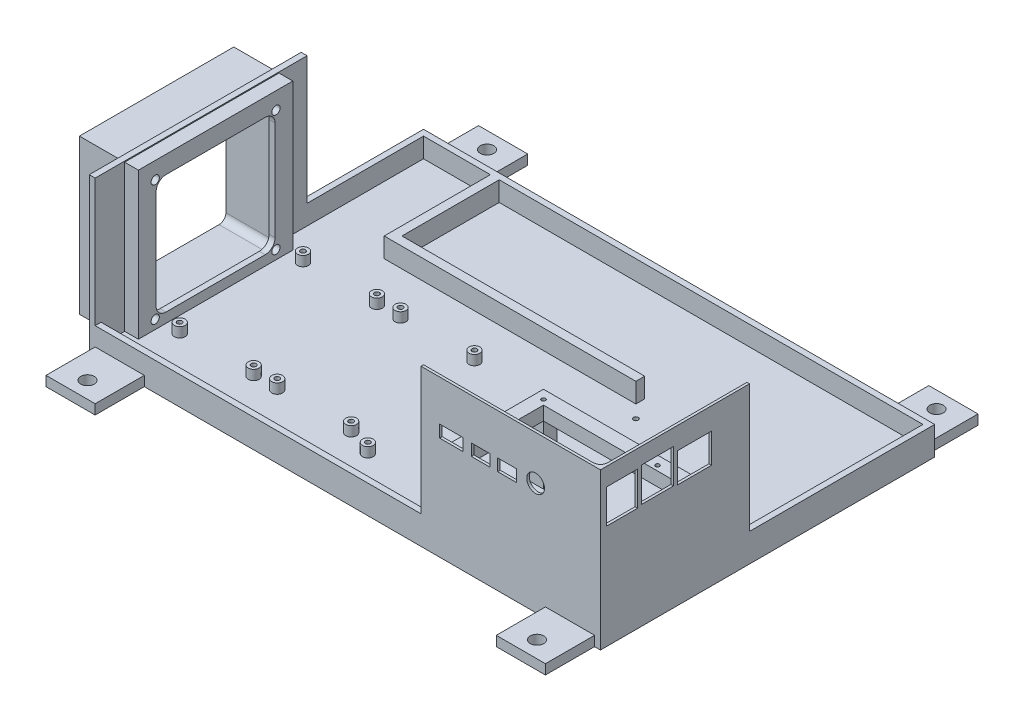
SolidWorks part; units mm, degrees
ref_plane "Front Plane" through (0, 0, 0) normal (0, 0, 1) x (1, 0, 0)
ref_plane "Top Plane" through (0, 0, 0) normal (0, 1, 0) x (1, 0, 0)
ref_plane "Right Plane" through (0, 0, 0) normal (1, 0, 0) x (0, 0, -1)
sketch "Sketch1" plane through (0, 0, 0) normal (0, 1, 0) x (1, 0, 0)
  line L1 (-130, -85) -> (130, -85)
  line L2 (-130, -85) -> (-130, 85)
  line L3 (-130, 85) -> (130, 85)
  line L4 (130, -85) -> (130, 85)
  line L5 (-130, -85) -> (130, 85) construction
  line L6 (-130, 85) -> (130, -85) construction
  point P0 (0, 0)
  dimension "D1" = 170
  dimension "D2" = 260
extrude "Floor" add sketch "Sketch1" along normal blind 4.3805
sketch "Sketch2" plane through (0, 4.3805, 0) normal (0, 1, 0) x (1, 0, 0)
  line L0 (127, -82) -> (127, 82)
  line L1 (127, 82) -> (-127, 82)
  line L2 (-127, 82) -> (-127, -82)
  line L3 (-127, -82) -> (127, -82)
  line L4 (130, -85) -> (130, 85)
  line L5 (130, 85) -> (-130, 85)
  line L6 (-130, 85) -> (-130, -85)
  line L7 (-130, -85) -> (130, -85)
  line L8 (130, -85) -> (130, 85)
  line L9 (130, 85) -> (-130, 85)
  line L10 (-130, 85) -> (-130, -85)
  line L11 (-130, -85) -> (130, -85)
  dimension "D1" = 0
  dimension "D2" = 3
extrude "Wall" add sketch "Sketch2" along normal blind 10
sketch "Sketch4" plane through (0, 4.3805, 0) normal (0, 1, 0) x (1, 0, 0)
  line L0 (120, -33) -> (49, -33)
  line L1 (127, -82) -> (42, -82)
  line L2 (127, -82) -> (127, -26)
  line L3 (127, -26) -> (42, -26)
  line L4 (42, -82) -> (42, -26)
  line L5 (49, -75) -> (49, -33)
  line L6 (120, -75) -> (49, -75)
  line L7 (120, -75) -> (120, -33)
  dimension "D1" = 85
  dimension "D2" = 56
  dimension "D3" = 7
extrude "Rpi stand" add sketch "Sketch4" along normal blind 7 from offset 30
sketch "Sketch7" plane through (0, 14.3805, 0) normal (0, 1, 0) x (1, 0, 0)
  line L0 (-127, 82) -> (-127, -82) construction
  line L1 (-130, -85) -> (-127, -85)
  line L2 (-130, -85) -> (-130, 22.7839)
  line L3 (-130, 22.7839) -> (-127, 22.7839)
  line L4 (-127, -85) -> (-127, 22.7839)
  line L5 (-127, -82) -> (127, -82) construction
  line L6 (130, -85) -> (38.7223, -85)
  line L7 (130, -85) -> (130, -52.9248)
  line L8 (127, -82) -> (38.7223, -82)
  line L9 (38.7223, -85) -> (38.7223, -82)
  line L10 (127, -82) -> (127, 82) construction
  line L12 (130, -52.9248) -> (130, -9.2525)
  line L13 (130, -9.2525) -> (127, -9.2525)
  line L14 (127, -82) -> (127, -9.2525)
  line L15 (-127, -82) -> (127, -82) construction
  line L16 (130, -85) -> (130, 85) construction
extrude "Temp support" add sketch "Sketch7" along normal blind 65
sketch "Sketch3" plane through (0, 0, 0) normal (0, 1, 0) x (1, 0, 0)
  line L0 (-114.3, 101.6) -> (114.3, 101.6) construction
  line L1 (-127, 85) -> (-102, 85)
  line L2 (-127, 85) -> (-127, 110)
  line L3 (-127, 110) -> (-102, 110)
  line L4 (-102, 85) -> (-102, 110)
  line L5 (127, 85) -> (102, 85)
  line L6 (127, 85) -> (127, 110)
  line L7 (127, 110) -> (102, 110)
  line L8 (102, 85) -> (102, 110)
  line L9 (-127, -85) -> (-102, -85)
  line L10 (-127, -85) -> (-127, -110)
  line L11 (-127, -110) -> (-102, -110)
  line L12 (-102, -85) -> (-102, -110)
  line L13 (127, -85) -> (102, -85)
  line L14 (127, -85) -> (127, -110)
  line L15 (127, -110) -> (102, -110)
  line L16 (102, -85) -> (102, -110)
  line L17 (114.3, 101.6) -> (114.3, -101.6) construction
  line L18 (114.3, -101.6) -> (-114.3, -101.6) construction
  line L19 (-114.3, -101.6) -> (-114.3, 101.6) construction
  line L20 (-130, 37.8738) -> (130, 37.8738) construction
  line L21 (130, 85) -> (-130, 85) construction
  line L22 (130, -9.2525) -> (130, 85) construction
  line L23 (0, 101.6) -> (0, -101.6) construction
  line L24 (-130, 22.7839) -> (-130, -85) construction
  line L29 (38.7223, -85) -> (130, -85) construction
  line L30 (-127, -85) -> (38.7223, -85) construction
  circle A0 centre (-114.3, 101.6) radius 3.429
  circle A1 centre (114.3, 101.6) radius 3.429
  circle A2 centre (114.3, -101.6) radius 3.429
  circle A3 centre (-114.3, -101.6) radius 3.429
  point P28 (-114.5, -85)
  point P29 (-102, -97.5)
  point P30 (114.5, -85)
  point P31 (-102, 97.5)
  dimension "D5" = 6.858
  dimension "D1" = 25
  dimension "D2" = 25
  dimension "D3" = 25
  dimension "D6" = 203.2
  dimension "D7" = 228.6
  dimension "D8" = 3
  dimension "D9" = 3
  dimension "D4" = 25
extrude "Brackets" add sketch "Sketch3" along normal blind 5
sketch "Sketch5" plane through (-130, 0, 0) normal (-1, 0, 0) x (0, 0, 1)
  line L0 (-8.5, 78.8805) -> (70, 78.8805)
  line L1 (-1, 4.3805) -> (62.5, 4.3805)
  line L2 (-4.5, 7.8805) -> (-4.5, 71.3805)
  line L3 (-1, 74.8805) -> (62.5, 74.8805)
  line L4 (66, 7.8805) -> (66, 71.3805)
  line L5 (70, 0.3805) -> (70, 78.8805)
  line L6 (-8.5, 0.3805) -> (70, 0.3805)
  line L7 (-8.5, 0.3805) -> (-8.5, 78.8805)
  line L8 (-4.5, 4.3805) -> (66, 4.3805) construction
  line L9 (110, 5) -> (110, 0) construction
  line L10 (-4.5, 4.3805) -> (-4.5, 74.8805) construction
  line L11 (-82, 4.3805) -> (82, 4.3805) construction
  line L12 (66, 4.3805) -> (66, 74.8805) construction
  line L13 (-4.5, 74.8805) -> (66, 74.8805) construction
  arc A0 (-1, 4.3805) -> (-4.5, 7.8805) centre (-1, 7.8805) cw
  arc A1 (62.5, 4.3805) -> (66, 7.8805) centre (62.5, 7.8805) ccw
  arc A2 (62.5, 74.8805) -> (66, 71.3805) centre (62.5, 71.3805) cw
  arc A3 (-4.5, 71.3805) -> (-1, 74.8805) centre (-1, 71.3805) cw
  dimension "D4" = 3.5
  dimension "D1" = 70.5
  dimension "D2" = 70.5
  dimension "D5" = 40
  dimension "D3" = 4
extrude "Fan Holder" add sketch "Sketch5" along normal blind 20 and the other way blind 10
sketch "Sketch8" plane through (-130, 0, 0) normal (-1, 0, 0) x (0, 0, 1)
  line L4 (-4.5, 71.3805) -> (-4.5, 7.8805)
  line L5 (-1, 4.3805) -> (62.5, 4.3805)
  line L6 (66, 7.8805) -> (66, 71.3805)
  line L7 (62.5, 74.8805) -> (-1, 74.8805)
  line L8 (-4.5, 71.3805) -> (-4.5, 7.8805)
  line L9 (-1, 4.3805) -> (62.5, 4.3805)
  line L10 (66, 7.8805) -> (66, 71.3805)
  line L20 (62.5, 74.8805) -> (-1, 74.8805)
  arc A2 (-4.5, 7.8805) -> (-1, 4.3805) centre (-1, 7.8805) ccw
  arc A3 (-4.5, 7.8805) -> (-1, 4.3805) centre (-1, 7.8805) ccw
  arc A4 (62.5, 4.3805) -> (66, 7.8805) centre (62.5, 7.8805) ccw
  arc A5 (62.5, 4.3805) -> (66, 7.8805) centre (62.5, 7.8805) ccw
  arc A8 (66, 71.3805) -> (62.5, 74.8805) centre (62.5, 71.3805) ccw
  arc A12 (66, 71.3805) -> (62.5, 74.8805) centre (62.5, 71.3805) ccw
  arc A14 (-1, 74.8805) -> (-4.5, 71.3805) centre (-1, 71.3805) ccw
  arc A15 (-1, 74.8805) -> (-4.5, 71.3805) centre (-1, 71.3805) ccw
  dimension "D1" = 0
extrude "Fan hole" cut sketch "Sketch8" against normal up to next (3 mm away)
sketch "Sketch11" plane through (-120, 0, 0) normal (-1, 0, 0) x (0, 0, 1)
  line L0 (-8.5, 39.6305) -> (70, 39.6305) construction
  line L1 (30.75, 78.8805) -> (30.75, 0.3805) construction
  line L3 (0.05, 8.9305) -> (61.45, 8.9305) construction
  line L4 (-8.5, 78.8805) -> (-8.5, 0.3805)
  line L5 (-8.5, 0.3805) -> (70, 0.3805)
  line L6 (70, 0.3805) -> (70, 78.8805)
  line L7 (70, 78.8805) -> (-8.5, 78.8805)
  line L8 (-8.5, 78.8805) -> (-8.5, 0.3805)
  line L9 (-8.5, 0.3805) -> (70, 0.3805)
  line L10 (70, 0.3805) -> (70, 78.8805)
  line L11 (70, 78.8805) -> (-8.5, 78.8805)
  line L12 (0.05, 8.9305) -> (0.05, 70.3305) construction
  line L13 (0.05, 70.3305) -> (61.45, 70.3305) construction
  line L14 (61.45, 8.9305) -> (61.45, 70.3305) construction
  line L15 (0.05, 8.9305) -> (61.45, 70.3305) construction
  line L16 (0.5, 69.8805) -> (0.5, 9.3805)
  line L17 (0.5, 9.3805) -> (61, 9.3805)
  line L18 (61, 9.3805) -> (61, 69.8805)
  line L19 (61, 69.8805) -> (0.5, 69.8805)
  line L20 (0.5, 64.8805) -> (0.5, 14.3805)
  line L21 (5.5, 9.3805) -> (56, 9.3805)
  line L22 (61, 14.3805) -> (61, 64.8805)
  line L23 (56, 69.8805) -> (5.5, 69.8805)
  line L24 (0.05, 70.3305) -> (61.45, 8.9305) construction
  arc A0 (0.5, 14.3805) -> (5.5, 9.3805) centre (5.5, 14.3805) ccw
  arc A1 (56, 9.3805) -> (61, 14.3805) centre (56, 14.3805) ccw
  arc A2 (61, 64.8805) -> (56, 69.8805) centre (56, 64.8805) ccw
  arc A3 (0.5, 64.8805) -> (5.5, 69.8805) centre (5.5, 64.8805) cw
  circle A4 centre (0.05, 70.3305) radius 2.1
  circle A5 centre (61.45, 70.3305) radius 2.1
  circle A6 centre (61.45, 8.9305) radius 2.1
  circle A7 centre (0.05, 8.9305) radius 2.1
  point P24 (30.75, 39.6305)
  point P34 (30.75, 39.6305)
  dimension "D3" = 5
  dimension "D6" = 4.2
  dimension "D4" = 61.4
  dimension "D5" = 61.4
  dimension "D1" = 0
  dimension "D2" = 9
extrude "Boss-Extrude9" add sketch "Sketch11" along normal blind 3
sketch "Sketch12" plane through (0, 34.3805, 0) normal (0, -1, 0) x (1, 0, 0)
  line L1 (42, 26) -> (49, 26)
  line L2 (42, 26) -> (42, 33)
  line L3 (42, 33) -> (49, 33)
  line L4 (49, 26) -> (49, 33)
  dimension "D1" = 7
  dimension "D2" = 7
extrude "Boss-Extrude10" add sketch "Sketch12" along normal up to next
sketch "Sketch13" plane through (0, 4.3805, 0) normal (0, 1, 0) x (1, 0, 0)
  line L0 (-127, -82) -> (127, -82) construction
  line L1 (-127, -85) -> (-127, 22.7839) construction
  line L2 (-112, -57) -> (-112, 5.7) construction
  line L3 (-112, 5.7) -> (-74.4, 5.7) construction
  line L4 (-112, -57) -> (-74.4, -57) construction
  line L5 (-74.4, 5.7) -> (-74.4, -57) construction
  line L6 (-74.4, 5.7) -> (-62.4, 5.7) construction
  line L7 (-62.4, 5.7) -> (-62.4, -57) construction
  line L8 (-62.4, -57) -> (-24.8, -57) construction
  line L9 (-24.8, -57) -> (-24.8, 5.7) construction
  line L10 (-24.8, 5.7) -> (-62.4, 5.7) construction
  line L11 (-74.4, -57) -> (-62.4, -57) construction
  line L12 (-24.8, -57) -> (62.83, -57) construction
  line L13 (62.83, -57) -> (62.83, -25.4) construction
  line L14 (62.83, -25.4) -> (105, -25.4) construction
  line L15 (105, -25.4) -> (105, -57) construction
  line L16 (105, -57) -> (62.83, -57) construction
  line L17 (118, 82) -> (118, 21.5) construction
  line L18 (-21.3, -57.85) -> (-21.3, 6.55) construction
  line L19 (127, 82) -> (-127, 82) construction
  line L20 (127, -9.2525) -> (127, 82) construction
  line L21 (118, 21.5) -> (120.7, 21.5) construction
  line L22 (118, 21.5) -> (41.5, 21.5) construction
  line L23 (-11.3, -62) -> (25.69, -62) construction
  line L24 (-11.3, -62) -> (-11.3, -21.4) construction
  line L25 (-11.3, -21.4) -> (25.69, -21.4) construction
  line L26 (25.69, -62) -> (25.69, -21.4) construction
  line L27 (-11.3, -62) -> (25.69, -21.4) construction
  line L28 (-11.3, -21.4) -> (25.69, -62) construction
  line L29 (130, -9.2525) -> (130, 85) construction
  line L30 (-127, -82) -> (38.7223, -82) construction
  circle A0 centre (-112, -57) radius 1.25
  circle A1 centre (-112, 5.7) radius 1.25
  circle A2 centre (-74.4, 5.7) radius 1.25
  circle A3 centre (-74.4, -57) radius 1.25
  circle A4 centre (-62.4, 5.7) radius 1.25
  circle A5 centre (-62.4, -57) radius 1.25
  circle A6 centre (-24.8, -57) radius 1.25
  circle A7 centre (-24.8, 5.7) radius 1.25
  circle A12 centre (120.7, 21.5) radius 1.25
  circle A13 centre (41.5, 21.5) radius 1.25
  circle A14 centre (-112, 5.7) radius 2.75
  circle A15 centre (-112, -57) radius 2.75
  circle A16 centre (-74.4, 5.7) radius 2.75
  circle A17 centre (-62.4, 5.7) radius 2.75
  circle A18 centre (-74.4, -57) radius 2.75
  circle A19 centre (-62.4, -57) radius 2.75
  circle A20 centre (-24.8, -57) radius 2.75
  circle A21 centre (-24.8, 5.7) radius 2.75
  circle A22 centre (62.83, -57) radius 2.5
  circle A23 centre (62.83, -25.4) radius 2.5
  circle A24 centre (105, -25.4) radius 2.5
  circle A25 centre (105, -57) radius 2.5
  circle A26 centre (-11.3, -62) radius 1.25
  circle A28 centre (-11.3, -62) radius 2.75
  circle A30 centre (-74.4, 5.7) radius 1.65 construction
  circle A31 centre (104.2333, -41.2) radius 1.5 construction
  circle A32 centre (104.2333, -41.2) radius 1.5 construction
  circle A33 centre (63.5933, -41.2) radius 1.5 construction
  circle A34 centre (63.5933, -41.2) radius 1.5 construction
  circle A35 centre (104.2333, -41.2) radius 3
  circle A36 centre (63.5933, -41.2) radius 3
  circle A37 centre (-11.3, -21.4) radius 1.25
  circle A38 centre (25.69, -21.4) radius 1.25
  circle A39 centre (25.69, -62) radius 1.25
  circle A40 centre (-11.3, -21.4) radius 2.75
  circle A41 centre (25.69, -21.4) radius 2.75
  circle A42 centre (25.69, -62) radius 2.75
  circle A43 centre (25.69, -21.4) radius 1.5 construction
  circle A44 centre (25.69, -21.4) radius 1.5 construction
  point P6 (-127, -31.108)
  point P8 (7.195, -41.7)
  dimension "D1" = 25
  dimension "D2" = 15
  dimension "D3" = 2.5
  dimension "D6" = 1.5
  dimension "D7" = 2.5
  dimension "D8" = 10
  dimension "D11" = 20
  dimension "D25" = 2.5
  dimension "D27" = 2.5
  dimension "D4" = 5
  dimension "D5" = 25
  dimension "D9" = 12
  dimension "D10" = 1.5
  dimension "D17" = 31.6
  dimension "D19" = 42.17
  dimension "D22" = 60.5
  dimension "D23" = 9
  dimension "D24" = 2.7
  dimension "D26" = 76.5
  dimension "D28" = 1.5
extrude "Built in Standoffs" add sketch "Sketch13" along normal blind 5 contours A1 | A16 A2 | A2 | A17 A4 | A4 | A14 A1 | A21 A7 | A7 | A15 A0 | A0 | A18 A3 | A3 | A19 A5 | A5 | A20 A6 | A6 | A22 | A23 | A24 A32 | A32 | A25 | A36 | A35 | A28 A26 | A26 | A40 A37 | A37 | A41 A38 | A38 | A42 A39 | A39 region at (-112, 4.3805, 57) region at (-112, 4.3805, -5.7) region at (-74.4, 4.3805, -5.7) region at (-74.4, 4.3805, 57) region at (-62.4, 4.3805, -5.7) region at (-62.4, 4.3805, 57) region at (-24.8, 4.3805, 57) region at (-24.8, 4.3805, -5.7) region at (-114.6722, 4.3805, -5.7) region at (-114.6722, 4.3805, 57) region at (-77.0722, 4.3805, -5.7) region at (-65.0722, 4.3805, -5.7) region at (-77.0722, 4.3805, 57) region at (-65.0722, 4.3805, 57) region at (-27.4722, 4.3805, 57) region at (-27.4722, 4.3805, -5.7) region at (62.83, 4.3805, 57) region at (62.83, 4.3805, 25.4) region at (105, 4.3805, 25.4) region at (105, 4.3805, 57) region at (-11.3, 4.3805, 62) region at (-13.9722, 4.3805, 62) region at (104.2333, 4.3805, 41.2) region at (63.5933, 4.3805, 41.2) region at (-11.3, 4.3805, 21.4) region at (25.69, 4.3805, 21.4) region at (25.69, 4.3805, 62) region at (-13.9722, 4.3805, 21.4) region at (23.0178, 4.3805, 21.4) region at (23.0178, 4.3805, 62)
sketch "Sketch19" plane through (0, 9.3805, 0) normal (0, 1, 0) x (1, 0, 0)
  circle A0 centre (104.2333, -41.2) radius 1.25
  circle A1 centre (63.5933, -41.2) radius 1.25
  dimension "D1" = 2.5
  dimension "D2" = 2.5
extrude "Bread board holes" cut sketch "Sketch19" against normal blind 7
sketch "Sketch14" plane through (0, 4.3805, 0) normal (0, 1, 0) x (1, 0, 0)
  line L0 (127, 82) -> (-88, 82)
  line L1 (127, 82) -> (-127, 82) construction
  line L2 (-88, 82) -> (-88, 32)
  line L3 (-88, 32) -> (127, 32)
  line L4 (127, -82) -> (127, 82) construction
  line L5 (127, 32) -> (127, 82)
  dimension "D1" = 215
  dimension "D2" = 50
extrude "Screw Holes" cut sketch "Sketch13<4>" against normal blind 7 from surface contours A37 | A38 | A26 | A39 | A1 | A0 | A3 | A5 | A2 | A4 | A7 | A6 | A32 region at (-11.3, 4.3805, 62) region at (-11.3, 4.3805, 21.4) region at (25.69, 4.3805, 21.4) region at (25.69, 4.3805, 62) starting at face at (-112, 9.3805, -2.95)
sketch "Sketch13<4>" plane through (0, 4.3805, 0) normal (0, 1, 0) x (1, 0, 0) same geometry as "Sketch13"
extrude "Driver Screw Holes" cut sketch "Sketch13<5>" against normal blind 3 contours A13 | A12
sketch "Sketch13<5>" plane through (0, 4.3805, 0) normal (0, 1, 0) x (1, 0, 0) same geometry as "Sketch13"
sketch "Sketch16" plane through (0, 4.3805, 0) normal (0, 1, 0) x (1, 0, 0)
  line L0 (-93, 82) -> (-93, 28)
  line L1 (-93, 28) -> (35, 28)
  line L2 (-88.5, 82) -> (-88.5, 32.5)
  line L3 (-88.5, 32.5) -> (35, 32.5)
  line L10 (-88, 82) -> (-88, 33) construction
  line L11 (-88, 33) -> (29.1074, 33) construction
  line L14 (-93, 28) -> (127, 28) construction
  line L16 (-88, 33) -> (127, 33) construction
  line L17 (-88.5, 82) -> (-93, 82)
  line L20 (35, 28) -> (35, 32.5)
  line L21 (-88.5, 32.5) -> (29.1074, 32.5) construction
  line L25 (-88, 33) -> (127, 33)
  line L26 (127, 33) -> (127, 82)
  line L27 (127, 82) -> (-88, 82)
  line L28 (-88, 82) -> (-88, 33)
  line L29 (-88, 33) -> (127, 33) construction
  line L30 (127, 33) -> (127, 82) construction
  line L31 (127, 82) -> (-88, 82) construction
  line L32 (-88, 82) -> (-88, 33) construction
  line L57 (-88, 82) -> (-88, 33) construction
  line L58 (127, 82) -> (-127, 82) construction
  dimension "D3" = 0.5
  dimension "D5" = 128
  dimension "D1" = 0
  dimension "D2" = 5
extrude "Power supply wall" add sketch "Sketch16" along normal blind 10 contours L2 L3 L20 L1 L0 L17
sketch "Sketch17" plane through (0, 41.3805, 0) normal (0, 1, 0) x (1, 0, 0)
  circle A0 centre (46.5, -30.5) radius 1.025
  circle A1 centre (104.5, -30.5) radius 1.025
  circle A2 centre (104.5, -79.5) radius 1.025
  circle A3 centre (46.5, -79.5) radius 1.025
  dimension "D1" = 2.05
extrude "Cut-Extrude3" cut sketch "Sketch17" against normal blind 6
sketch "Sketch20" plane through (0, 0, 85) normal (0, 0, 1) x (1, 0, 0)
  line L1 (49.6827, 57.1504) -> (58.6882, 57.1504) construction
  line L2 (49.6827, 57.1504) -> (49.6827, 53.9554) construction
  line L3 (49.6827, 53.9554) -> (58.6882, 53.9554) construction
  line L4 (58.6882, 57.1504) -> (58.6882, 53.9554) construction
  line L5 (79.2167, 56.9908) -> (85.8798, 56.9908) construction
  line L6 (79.2167, 56.9908) -> (79.2167, 53.9258) construction
  line L7 (79.2167, 53.9258) -> (85.8798, 53.9258) construction
  line L8 (85.8798, 56.9908) -> (85.8798, 53.9258) construction
  line L9 (65.7798, 56.9112) -> (72.2962, 56.9112) construction
  line L10 (65.7798, 56.9112) -> (65.7798, 53.9475) construction
  line L11 (65.7798, 53.9475) -> (72.2962, 53.9475) construction
  line L12 (72.2962, 56.9112) -> (72.2962, 53.9475) construction
  line L13 (48.1827, 58.6504) -> (60.1882, 58.6504)
  line L14 (60.1882, 58.6504) -> (60.1882, 52.4554)
  line L15 (48.1827, 52.4554) -> (60.1882, 52.4554)
  line L16 (48.1827, 58.6504) -> (48.1827, 52.4554)
  line L17 (77.7167, 58.4908) -> (87.3798, 58.4908)
  line L18 (87.3798, 58.4908) -> (87.3798, 52.4258)
  line L19 (77.7167, 52.4258) -> (87.3798, 52.4258)
  line L20 (77.7167, 58.4908) -> (77.7167, 52.4258)
  line L21 (64.2798, 58.4112) -> (73.7962, 58.4112)
  line L22 (73.7962, 58.4112) -> (73.7962, 52.4475)
  line L23 (64.2798, 52.4475) -> (73.7962, 52.4475)
  line L24 (64.2798, 58.4112) -> (64.2798, 52.4475)
  circle A0 centre (97, 56.9705) radius 4.5
  dimension "D1" = 9
  dimension "D2" = 1.5
extrude "Cut-Extrude5" cut sketch "Sketch20" against normal up to next
sketch "Sketch21" plane through (0, 79.3805, 0) normal (0, 1, 0) x (1, 0, 0)
  line L0 (125, -26.3) -> (46, -26.3) construction
  line L1 (42.3, -30) -> (42.3, -80) construction
  line L2 (46, -83.7) -> (125, -83.7)
  line L3 (128.7, -80) -> (128.7, -30)
  line L4 (128, -80) -> (128, -30)
  line L5 (125, -27) -> (46, -27)
  line L6 (43, -30) -> (43, -80)
  line L7 (46, -83) -> (125, -83)
  line L8 (128, -80) -> (128, -30) construction
  line L9 (125, -27) -> (46, -27) construction
  line L10 (43, -30) -> (43, -80) construction
  line L11 (46, -83) -> (125, -83) construction
  line L28 (46, -83.7) -> (37.0142, -83.7)
  line L29 (37.0142, -83.7) -> (37.0142, -5.7053)
  line L30 (37.0142, -5.7053) -> (128.7, -5.7053)
  line L31 (128.7, -5.7053) -> (128.7, -30)
  arc A0 (46, -26.3) -> (42.3, -30) centre (46, -30) ccw construction
  arc A1 (42.3, -80) -> (46, -83.7) centre (46, -80) ccw construction
  arc A2 (125, -83.7) -> (128.7, -80) centre (125, -80) ccw
  arc A3 (128.7, -30) -> (125, -26.3) centre (125, -30) ccw construction
  arc A4 (128, -30) -> (125, -27) centre (125, -30) ccw
  arc A5 (46, -27) -> (43, -30) centre (46, -30) ccw
  arc A6 (43, -80) -> (46, -83) centre (46, -80) ccw
  arc A7 (125, -83) -> (128, -80) centre (125, -80) ccw
  arc A8 (128, -30) -> (125, -27) centre (125, -30) ccw construction
  arc A9 (46, -27) -> (43, -30) centre (46, -30) ccw construction
  arc A10 (43, -80) -> (46, -83) centre (46, -80) ccw construction
  arc A11 (125, -83) -> (128, -80) centre (125, -80) ccw construction
  dimension "D1" = 0
  dimension "D2" = 0.7
extrude "Cut-Extrude6" cut sketch "Sketch21" against normal blind 35 contours L2 A2 L3 L31 L30 L29 L28
sketch "Sketch22" plane through (130, 0, 0) normal (1, 0, 0) x (0, 0, -1)
  line L0 (-81.966, 70.2905) -> (-66.1499, 70.2905)
  line L1 (-81.166, 69.4905) -> (-66.9499, 69.4905) construction
  line L2 (-81.166, 69.4905) -> (-81.166, 53.8427) construction
  line L3 (-81.166, 53.8427) -> (-66.9499, 53.8427) construction
  line L4 (-66.9499, 69.4905) -> (-66.9499, 53.8427) construction
  line L5 (-63.3011, 70.2905) -> (-48.6526, 70.2905) construction
  line L6 (-63.3011, 70.2905) -> (-63.3011, 54.5222) construction
  line L7 (-63.3011, 54.5222) -> (-48.6526, 54.5222) construction
  line L8 (-48.6526, 70.2905) -> (-48.6526, 54.5222) construction
  line L9 (-45.1414, 67.4119) -> (-29.3586, 67.4119) construction
  line L10 (-45.1414, 67.4119) -> (-45.1414, 53.9605) construction
  line L11 (-45.1414, 53.9605) -> (-29.3586, 53.9605) construction
  line L12 (-29.3586, 67.4119) -> (-29.3586, 53.9605) construction
  line L13 (-66.1499, 70.2905) -> (-66.1499, 53.0427)
  line L14 (-81.966, 53.0427) -> (-66.1499, 53.0427)
  line L15 (-81.966, 70.2905) -> (-81.966, 53.0427)
  line L16 (-64.1011, 71.0905) -> (-47.8526, 71.0905)
  line L17 (-47.8526, 71.0905) -> (-47.8526, 53.7222)
  line L18 (-64.1011, 53.7222) -> (-47.8526, 53.7222)
  line L19 (-64.1011, 71.0905) -> (-64.1011, 53.7222)
  line L20 (-45.9414, 68.2119) -> (-28.5586, 68.2119)
  line L21 (-28.5586, 68.2119) -> (-28.5586, 53.1605)
  line L22 (-45.9414, 53.1605) -> (-28.5586, 53.1605)
  line L23 (-45.9414, 68.2119) -> (-45.9414, 53.1605)
  line L24 (-70.9672, 69.4905) -> (-73.95, 69.4905) construction
  line L25 (-85, 79.3805) -> (-85, 0) construction
  line L26 (-85, 0) -> (85, 0) construction
  arc A0 (-29.3, 67.2705) -> (-29.5, 67.4705) centre (-29.5, 67.2705) ccw construction
  dimension "D2" = 3.834
  dimension "D3" = 14.2161
  dimension "D4" = 15.6478
  dimension "D5" = 3.6488
  dimension "D6" = 14.6485
  dimension "D7" = 15.7683
  dimension "D8" = 70.2905
  dimension "D9" = 13.4514
  dimension "D1" = 0.8
extrude "Cut-Extrude7" cut sketch "Sketch22" against normal up to next
equation "\"D2@Sketch3\"=\"D1@Sketch3\""
